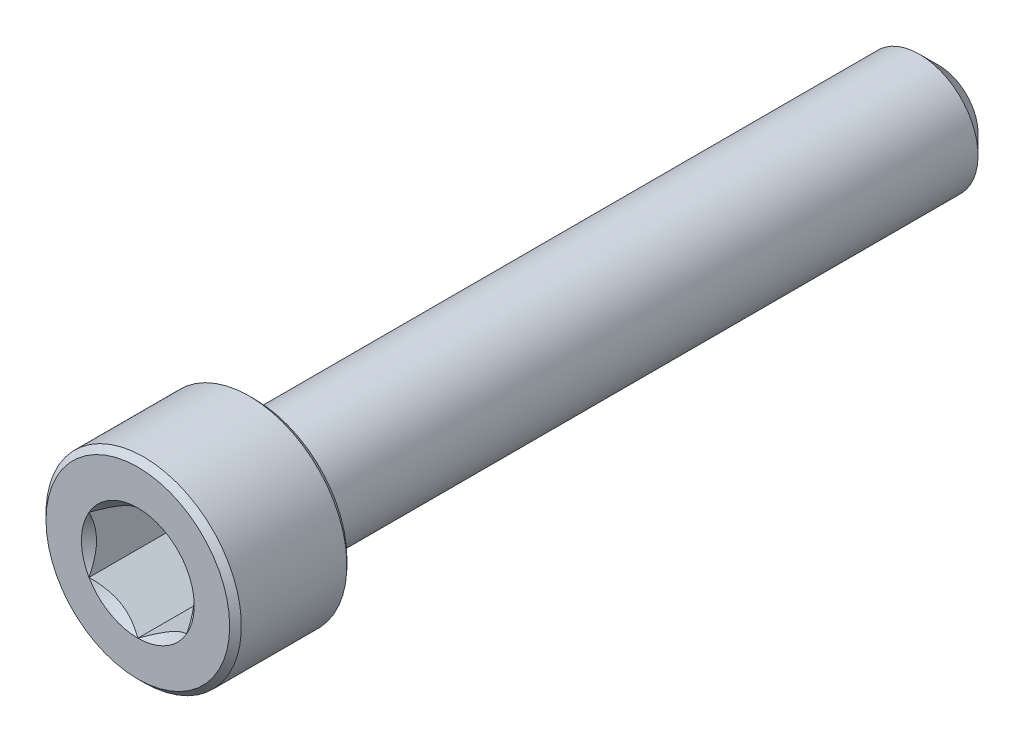
SolidWorks part; units mm, degrees
material "Alloy Steel"
ref_plane "Front Plane" through (0, 0, 0) normal (0, 0, 1) x (1, 0, 0)
ref_plane "Top Plane" through (0, 0, 0) normal (0, 1, 0) x (1, 0, 0)
ref_plane "Right Plane" through (0, 0, 0) normal (1, 0, 0) x (0, 0, -1)
sketch "Sketch1" plane through (0, 0, 0) normal (1, 0, 0) x (0, 0, -1)
  line L0 (-20.5, 0) -> (20.5, 0) construction
  line L1 (20.5, 0) -> (20.5, 2) construction
  line L2 (20.5, 2) -> (19.5, 3) construction
  line L3 (19.5, 3) -> (19.75, 3) construction
  line L4 (19.75, 3) -> (-14.5, 3) construction
  line L5 (-14.5, 3) -> (-14.5, 5) construction
  line L6 (-14.5, 5) -> (-20.5, 5) construction
  line L7 (-20.5, 5) -> (-20.5, 0) construction
  line L8 (20.5, 2) -> (20.5, 3) construction
  line L9 (20.4375, 3.1083) -> (20.9375, 2.2422) construction
  line L10 (20.9375, 2.2422) -> (21.4375, 3.1083) construction
  line L11 (21.4375, 3.1083) -> (20.4375, 3.1083) construction
  line L12 (20.9375, 3.1083) -> (20.9375, 3) construction
  line L13 (20.9375, 2.2422) -> (20.9375, 2.3505) construction
  line L14 (20.875, 2.3505) -> (21, 2.3505) construction
  line L15 (20.5, 3) -> (21.375, 3) construction
  line L16 (20.4688, 3.0541) -> (21.4062, 3.0541) construction
  line L17 (20.5, 0) -> (20.5, -3) construction
  line L18 (-14.8, 5) -> (-14.5, 4.7) construction
  line L19 (-20.2, 5) -> (-20.5, 4.7) construction
  line L20 (-14.5, 3) -> (-14.5, 0) construction
  line L21 (-14.5, 1.5) -> (-2.8333, 1.5) construction
  line L22 (-2.8333, 1.5) -> (8.8333, 1.5) construction
  line L23 (8.8333, 1.5) -> (20.5, 1.5) construction
  line L24 (-2.8333, 1.5) -> (-2.8333, 3) construction
  line L25 (-2.8333, 3) -> (-2.8333, 5) construction
  line L26 (8.8333, 1.5) -> (8.8333, 5) construction
  point P0 (-20.5, 2.5)
  point P3 (18, 3)
  point P4 (0, 0)
  point P18 (8.8333, 3)
  point P22 (20.9375, 2.3505)
  point P24 (19.75, 3)
  point P25 (20.9375, 3)
  point P28 (20.9375, 3.0541)
  point P29 (18, -3)
  point P30 (-2.8333, 3)
  point P31 (-17.5, 5)
  point P37 (-15.55, 5)
  point P38 (-20.05, 5)
  point P45 (-2.8333, 1.5)
  point P46 (8.8333, 1.5)
  dimension "D1" = 45
  dimension "D2" = 0.125
  dimension "D3" = 1
  dimension "D7" = 0.3
  dimension "D8" = 0.3
  dimension "D9" = 0.3
  dimension "D10" = 0.15
  dimension "D11" = 0.75
  dimension "Drive Size" = 5
  dimension "Head Diameter" = 10
  dimension "Head Height" = 6
  dimension "Thread Pitch" = 1
  dimension "Thread Major Diameter" = 6
  dimension "Length" = 35
  dimension "D12" = 0.75
  dimension "D4" = 2.5
sketch "Sketch2" plane through (0, 0, 0) normal (1, 0, 0) x (0, 0, -1)
  line L0 (-20.5, 0) -> (-20.5, 4.7)
  line L1 (-20.2, 5) -> (-14.8, 5)
  line L2 (-14.5, 4.7) -> (-14.5, 3)
  line L3 (-14.5, 3) -> (19.5, 3)
  line L4 (19.5, 3) -> (20.5, 2)
  line L5 (20.5, 2) -> (20.5, 0)
  line L6 (-14.8, 5) -> (-14.5, 4.7) construction
  line L7 (20.5, 0) -> (-20.5, 0)
  line L8 (-20.2, 5) -> (-20.5, 4.7) construction
  line L9 (-14.8, 5) -> (-14.5, 4.7)
  line L10 (-20.2, 5) -> (-20.5, 4.7)
revolve "Revolve1" add sketch "Sketch2" angle 360 about L7
sketch "Sketch3" plane through (0, 0, 20.5) normal (0, 0, 1) x (1, 0, 0)
  line L1 (2.5, -1.4434) -> (2.5, 1.4434)
  line L2 (2.5, 1.4434) -> (0, 2.8868)
  line L3 (0, 2.8868) -> (-2.5, 1.4434)
  line L4 (-2.5, 1.4434) -> (-2.5, -1.4434)
  line L5 (-2.5, -1.4434) -> (0, -2.8868)
  line L6 (0, -2.8868) -> (2.5, -1.4434)
  circle A0 centre (0, 0) radius 2.5 construction
extrude "Cut-Extrude1" cut sketch "Sketch3" against normal offset from surface (5 mm away) 1 up to face at (0, 4.7, 14.5)
sketch "Sketch4" plane through (0, 0, 20.5) normal (0, 0, 1) x (1, 0, 0)
  circle A0 centre (0, 0) radius 2.8868
extrude "Cut-Extrude2" cut sketch "Sketch4" against normal up to vertex (3 mm away) draft 45 up to point (0, 5, 17.5)
ref_plane "Plane1" [suppressed] through (0, 0, -19.75) normal (0, 0, 1) x (1, 0, 0)
split "Split1" [suppressed] bodies to split 106
sketch "Sketch6" [suppressed] plane through (0, 0, -20.5) normal (0, 0, -1) x (-1, 0, 0)
  circle A0 centre (0, 0) radius 3
curve "Helix/Spiral1" [suppressed] pitch 1 height 36.15 turns 36.15
sketch "Sketch7" [suppressed] plane through (0, 0, 0) normal (1, 0, 0) x (0, 0, -1)
  line L0 (20.4688, 3.0541) -> (21.4062, 3.0541)
  line L1 (21.4062, 3.0541) -> (21, 2.3505)
  line L2 (21, 2.3505) -> (20.875, 2.3505)
  line L3 (20.875, 2.3505) -> (20.4688, 3.0541)
sweep "Cut-Sweep1" [suppressed] cut profiles "Sketch7" path "Helix/Spiral1"
sketch "Sketch8" [suppressed] plane through (0, 0, 14.5) normal (0, 0, -1) x (-1, 0, 0)
  circle A0 centre (0, 0) radius 3
extrude "Boss-Extrude1" [suppressed] add sketch "Sketch8" along normal through all draft 45
equation "\"D2@Sketch1\" = \"Thread Pitch@Sketch1\" / 8"
equation "\"D3@Sketch1\"= \"Thread Pitch@Sketch1\""
equation "\"D4@Helix/Spiral1\" = \"Thread Pitch@Sketch1\""
equation "\"D7@Sketch1\" = \"Head Height@Sketch1\" * .05"
equation "\"D8@Sketch1\"=\"D7@Sketch1\""
equation "\"D9@Sketch1\"=\"D7@Sketch1\""
equation "\"D10@Sketch1\"=\"D7@Sketch1\"/2"
equation "\"D11@Sketch1\"=\"D10@Sketch1\"*5"
equation "\"D4@Sketch1\"=\"Thread Pitch@Sketch1\"*2.5"
equation "\"D12@Sketch1\"=\"Thread Pitch@Sketch1\"*.75"
